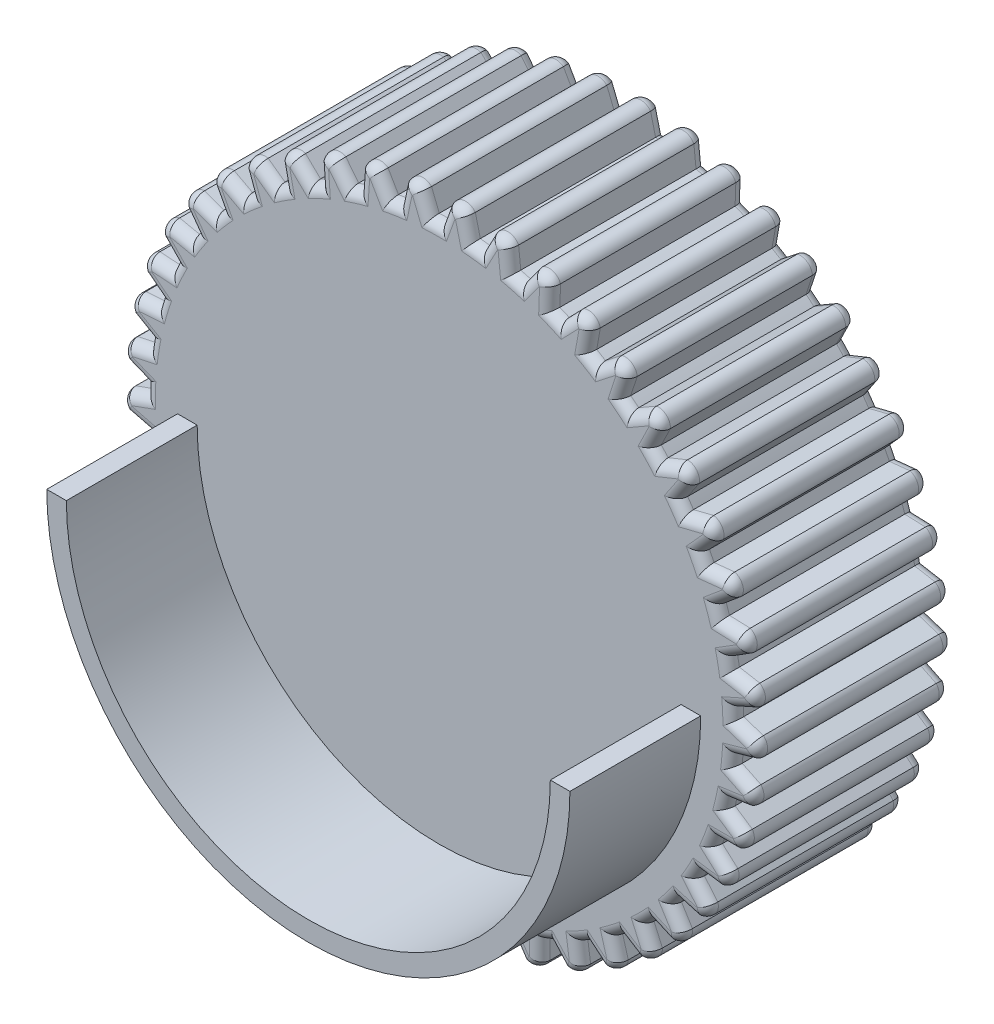
SolidWorks part; units mm, degrees
ref_plane "Front Plane" through (0, 0, 0) normal (0, 0, 1) x (1, 0, 0)
ref_plane "Top Plane" through (0, 0, 0) normal (0, 1, 0) x (1, 0, 0)
ref_plane "Right Plane" through (0, 0, 0) normal (1, 0, 0) x (0, 0, -1)
sketch "Sketch1" plane through (0, 0, 0) normal (0, 0, 1) x (1, 0, 0)
  circle A0 centre (0, 0) radius 22.5
  dimension "D1" = 45
extrude "Boss-Extrude1" add sketch "Sketch1" along normal blind 15
sketch "Sketch2" plane through (0, 0, 15) normal (0, 0, 1) x (1, 0, 0)
  circle A0 centre (0, 0) radius 20.25
  circle A1 centre (0, 0) radius 18.5
  dimension "D1" = 40.5
  dimension "D2" = 37
extrude "Boss-Extrude2" add sketch "Sketch2" along normal blind 10
sketch "Sketch3" plane through (0, 0, 15) normal (0, 0, 1) x (1, 0, 0)
  line L0 (0, 22.5) -> (0.5437, 23.9938)
  line L2 (2.3519, 22.3767) -> (1.9673, 23.9192)
  line L3 (0, 0) -> (0, 22.5)
  line L4 (2.3519, 22.3767) -> (0, 0)
  line L5 (0.5437, 23.9938) -> (1.9673, 23.9192)
  line L6 (0, 22.5) -> (0.5437, 23.9938)
  line L7 (1.9673, 23.9192) -> (2.3519, 22.3767)
  line L8 (3.1314, 22.281) -> (3.8777, 23.6847)
  line L9 (3.8777, 23.6847) -> (5.2771, 23.4127)
  line L10 (5.4432, 21.8317) -> (5.2771, 23.4127)
  line L11 (6.2018, 21.6284) -> (7.1362, 22.9145)
  line L12 (7.1362, 22.9145) -> (8.4841, 22.4504)
  line L13 (8.4286, 20.8616) -> (8.4841, 22.4504)
  line L14 (9.1516, 20.5548) -> (10.2559, 21.6983)
  line L15 (10.2559, 21.6983) -> (11.5261, 21.0511)
  line L16 (11.25, 19.4856) -> (11.5261, 21.0511)
  line L17 (11.9232, 19.0811) -> (13.1759, 20.0598)
  line L18 (13.1759, 20.0598) -> (14.3436, 19.2421)
  line L19 (13.8524, 17.7302) -> (14.3436, 19.2421)
  line L20 (14.4627, 17.236) -> (15.8395, 18.0309)
  line L21 (15.8395, 18.0309) -> (16.882, 17.0586)
  line L22 (16.1851, 15.6298) -> (16.882, 17.0586)
  line L23 (16.7208, 15.0554) -> (18.1947, 15.651)
  line L24 (18.1947, 15.651) -> (19.0918, 14.5431)
  line L25 (18.2029, 13.2252) -> (19.0918, 14.5431)
  line L26 (18.6533, 12.5818) -> (20.1958, 12.9664)
  line L27 (20.1958, 12.9664) -> (20.93, 11.7445)
  line L28 (19.8663, 10.5631) -> (20.93, 11.7445)
  line L29 (20.2229, 9.8634) -> (21.8039, 10.0295)
  line L30 (21.8039, 10.0295) -> (22.3609, 8.7173)
  line L31 (21.1431, 7.6955) -> (22.3609, 8.7173)
  line L32 (21.3988, 6.9529) -> (22.9875, 6.8974)
  line L33 (22.9875, 6.8974) -> (23.3565, 5.5204)
  line L34 (22.0083, 4.678) -> (23.3565, 5.5204)
  line L35 (22.1582, 3.9071) -> (23.7237, 3.631)
  line L36 (23.7237, 3.631) -> (23.8975, 2.2161)
  line L37 (22.4452, 1.5695) -> (23.8975, 2.2161)
  line L38 (22.4863, 0.7852) -> (23.9982, 0.294)
  line L39 (23.9982, 0.294) -> (23.9733, -1.1313)
  line L40 (22.4452, -1.5695) -> (23.9733, -1.1313)
  line L41 (22.3767, -2.3519) -> (23.8056, -3.0488)
  line L42 (23.8056, -3.0488) -> (23.5826, -4.4568)
  line L43 (22.0083, -4.678) -> (23.5826, -4.4568)
  line L44 (21.8317, -5.4432) -> (23.1496, -6.3322)
  line L45 (23.1496, -6.3322) -> (22.7328, -7.6955)
  line L46 (21.1431, -7.6955) -> (22.7328, -7.6955)
  line L47 (20.8616, -8.4286) -> (22.043, -9.4924)
  line L48 (22.043, -9.4924) -> (21.4406, -10.7844)
  line L49 (19.8663, -10.5631) -> (21.4406, -10.7844)
  line L50 (19.4856, -11.25) -> (20.5074, -12.4678)
  line L51 (20.5074, -12.4678) -> (19.731, -13.6634)
  line L52 (18.2029, -13.2252) -> (19.731, -13.6634)
  line L53 (17.7302, -13.8524) -> (18.5727, -15.2005)
  line L54 (18.5727, -15.2005) -> (17.6374, -16.2764)
  line L55 (16.1851, -15.6298) -> (17.6374, -16.2764)
  line L56 (15.6298, -16.1851) -> (16.2764, -17.6374)
  line L57 (16.2764, -17.6374) -> (15.2005, -18.5727)
  line L58 (13.8524, -17.7302) -> (15.2005, -18.5727)
  line L59 (13.2252, -18.2029) -> (13.6634, -19.731)
  line L60 (13.6634, -19.731) -> (12.4678, -20.5074)
  line L61 (11.25, -19.4856) -> (12.4678, -20.5074)
  line L62 (10.5631, -19.8663) -> (10.7844, -21.4406)
  line L63 (10.7844, -21.4406) -> (9.4924, -22.043)
  line L64 (8.4286, -20.8616) -> (9.4924, -22.043)
  line L65 (7.6955, -21.1431) -> (7.6955, -22.7328)
  line L66 (7.6955, -22.7328) -> (6.3322, -23.1496)
  line L67 (5.4432, -21.8317) -> (6.3322, -23.1496)
  line L68 (4.678, -22.0083) -> (4.4568, -23.5826)
  line L69 (4.4568, -23.5826) -> (3.0488, -23.8056)
  line L70 (2.3519, -22.3767) -> (3.0488, -23.8056)
  line L71 (1.5695, -22.4452) -> (1.1313, -23.9733)
  line L72 (1.1313, -23.9733) -> (-0.294, -23.9982)
  line L73 (-0.7852, -22.4863) -> (-0.294, -23.9982)
  line L74 (-1.5695, -22.4452) -> (-2.2161, -23.8975)
  line L75 (-2.2161, -23.8975) -> (-3.631, -23.7237)
  line L76 (-3.9071, -22.1582) -> (-3.631, -23.7237)
  line L77 (-4.678, -22.0083) -> (-5.5204, -23.3565)
  line L78 (-5.5204, -23.3565) -> (-6.8974, -22.9875)
  line L79 (-6.9529, -21.3988) -> (-6.8974, -22.9875)
  line L80 (-7.6955, -21.1431) -> (-8.7173, -22.3609)
  line L81 (-8.7173, -22.3609) -> (-10.0295, -21.8039)
  line L82 (-9.8634, -20.2229) -> (-10.0295, -21.8039)
  line L83 (-10.5631, -19.8663) -> (-11.7445, -20.93)
  line L84 (-11.7445, -20.93) -> (-12.9664, -20.1958)
  line L85 (-12.5818, -18.6533) -> (-12.9664, -20.1958)
  line L86 (-13.2252, -18.2029) -> (-14.5431, -19.0918)
  line L87 (-14.5431, -19.0918) -> (-15.651, -18.1947)
  line L88 (-15.0554, -16.7208) -> (-15.651, -18.1947)
  line L89 (-15.6298, -16.1851) -> (-17.0586, -16.882)
  line L90 (-17.0586, -16.882) -> (-18.0309, -15.8395)
  line L91 (-17.236, -14.4627) -> (-18.0309, -15.8395)
  line L92 (-17.7302, -13.8524) -> (-19.2421, -14.3436)
  line L93 (-19.2421, -14.3436) -> (-20.0598, -13.1759)
  line L94 (-19.0811, -11.9232) -> (-20.0598, -13.1759)
  line L95 (-19.4856, -11.25) -> (-21.0511, -11.5261)
  line L96 (-21.0511, -11.5261) -> (-21.6983, -10.2559)
  line L97 (-20.5548, -9.1516) -> (-21.6983, -10.2559)
  line L98 (-20.8616, -8.4286) -> (-22.4504, -8.4841)
  line L99 (-22.4504, -8.4841) -> (-22.9145, -7.1362)
  line L100 (-21.6284, -6.2018) -> (-22.9145, -7.1362)
  line L101 (-21.8317, -5.4432) -> (-23.4127, -5.2771)
  line L102 (-23.4127, -5.2771) -> (-23.6847, -3.8777)
  line L103 (-22.281, -3.1314) -> (-23.6847, -3.8777)
  line L104 (-22.3767, -2.3519) -> (-23.9192, -1.9673)
  line L105 (-23.9192, -1.9673) -> (-23.9938, -0.5437)
  line L106 (-22.5, 0) -> (-23.9938, -0.5437)
  line L107 (-22.4863, 0.7852) -> (-23.9602, 1.3808)
  line L108 (-23.9602, 1.3808) -> (-23.836, 2.8009)
  line L109 (-22.281, 3.1314) -> (-23.836, 2.8009)
  line L110 (-22.1582, 3.9071) -> (-23.5349, 4.7019)
  line L111 (-23.5349, 4.7019) -> (-23.2142, 6.0909)
  line L112 (-21.6284, 6.2018) -> (-23.2142, 6.0909)
  line L113 (-21.3988, 6.9529) -> (-22.6515, 7.9316)
  line L114 (-22.6515, 7.9316) -> (-22.1406, 9.2625)
  line L115 (-20.5548, 9.1516) -> (-22.1406, 9.2625)
  line L116 (-20.2229, 9.8634) -> (-21.3272, 11.0069)
  line L117 (-21.3272, 11.0069) -> (-20.6361, 12.2537)
  line L118 (-19.0811, 11.9232) -> (-20.6361, 12.2537)
  line L119 (-18.6533, 12.5818) -> (-19.5878, 13.8679)
  line L120 (-19.5878, 13.8679) -> (-18.7298, 15.0064)
  line L121 (-17.236, 14.4627) -> (-18.7298, 15.0064)
  line L122 (-16.7208, 15.0554) -> (-17.4671, 16.4591)
  line L123 (-17.4671, 16.4591) -> (-16.4591, 17.4671)
  line L124 (-15.0554, 16.7208) -> (-16.4591, 17.4671)
  line L125 (-14.4627, 17.236) -> (-15.0064, 18.7298)
  line L126 (-15.0064, 18.7298) -> (-13.8679, 19.5878)
  line L127 (-12.5818, 18.6533) -> (-13.8679, 19.5878)
  line L128 (-11.9232, 19.0811) -> (-12.2537, 20.6361)
  line L129 (-12.2537, 20.6361) -> (-11.0069, 21.3272)
  line L130 (-9.8634, 20.2229) -> (-11.0069, 21.3272)
  line L131 (-9.1516, 20.5548) -> (-9.2625, 22.1406)
  line L132 (-9.2625, 22.1406) -> (-7.9316, 22.6515)
  line L133 (-6.9529, 21.3988) -> (-7.9316, 22.6515)
  line L134 (-6.2018, 21.6284) -> (-6.0909, 23.2142)
  line L135 (-6.0909, 23.2142) -> (-4.7019, 23.5349)
  line L136 (-3.9071, 22.1582) -> (-4.7019, 23.5349)
  line L137 (-3.1314, 22.281) -> (-2.8009, 23.836)
  line L138 (-2.8009, 23.836) -> (-1.3808, 23.9602)
  line L139 (-0.7852, 22.4863) -> (-1.3808, 23.9602)
  arc A0 (0, 22.5) -> (2.3519, 22.3767) centre (0, 0) cw
  circle A1 centre (0, 0) radius 22.5 construction
  circle A2 centre (0, 0) radius 18.5 construction
  arc A4 (0.5437, 23.9938) -> (1.9673, 23.9192) centre (1.2243, 23.3613) cw
  arc A5 (0, 22.5) -> (2.3519, 22.3767) centre (0, 0) cw
  arc A6 (3.1314, 22.281) -> (5.4432, 21.8317) centre (0, 0) cw
  arc A7 (3.8777, 23.6847) -> (5.2771, 23.4127) centre (4.4637, 22.9636) cw
  arc A8 (6.2018, 21.6284) -> (8.4286, 20.8616) centre (0, 0) cw
  arc A9 (7.1362, 22.9145) -> (8.4841, 22.4504) centre (7.6161, 22.1189) cw
  arc A10 (9.1516, 20.5548) -> (11.25, 19.4856) centre (0, 0) cw
  arc A11 (10.2559, 21.6983) -> (11.5261, 21.0511) centre (10.6204, 20.8437) cw
  arc A12 (11.9232, 19.0811) -> (13.8524, 17.7302) centre (0, 0) cw
  arc A13 (13.1759, 20.0598) -> (14.3436, 19.2421) centre (13.4179, 19.1628) cw
  arc A14 (14.4627, 17.236) -> (16.1851, 15.6298) centre (0, 0) cw
  arc A15 (15.8395, 18.0309) -> (16.882, 17.0586) centre (15.9543, 17.1089) cw
  arc A16 (16.7208, 15.0554) -> (18.2029, 13.2252) centre (0, 0) cw
  arc A17 (18.1947, 15.651) -> (19.0918, 14.5431) centre (18.1801, 14.7219) cw
  arc A18 (18.6533, 12.5818) -> (19.8663, 10.5631) centre (0, 0) cw
  arc A19 (20.1958, 12.9664) -> (20.93, 11.7445) centre (20.0521, 12.0485) cw
  arc A20 (20.2229, 9.8634) -> (21.1431, 7.6955) centre (0, 0) cw
  arc A21 (21.8039, 10.0295) -> (22.3609, 8.7173) centre (21.5337, 9.1405) cw
  arc A22 (21.3988, 6.9529) -> (22.0083, 4.678) centre (0, 0) cw
  arc A23 (22.9875, 6.8974) -> (23.3565, 5.5204) centre (22.5963, 6.0547) cw
  arc A24 (22.1582, 3.9071) -> (22.4452, 1.5695) centre (0, 0) cw
  arc A25 (23.7237, 3.631) -> (23.8975, 2.2161) centre (23.219, 2.8509) cw
  arc A26 (22.4863, 0.7852) -> (22.4452, -1.5695) centre (0, 0) cw
  arc A27 (23.9982, 0.294) -> (23.9733, -1.1313) centre (23.3898, -0.4083) cw
  arc A28 (22.3767, -2.3519) -> (22.0083, -4.678) centre (0, 0) cw
  arc A29 (23.8056, -3.0488) -> (23.5826, -4.4568) centre (23.1054, -3.6595) cw
  arc A30 (21.8317, -5.4432) -> (21.1431, -7.6955) centre (0, 0) cw
  arc A31 (23.1496, -6.3322) -> (22.7328, -7.6955) centre (22.3712, -6.8396) cw
  arc A32 (20.8616, -8.4286) -> (19.8663, -10.5631) centre (0, 0) cw
  arc A33 (22.043, -9.4924) -> (21.4406, -10.7844) centre (21.2016, -9.8865) cw
  arc A34 (19.4856, -11.25) -> (18.2029, -13.2252) centre (0, 0) cw
  arc A35 (20.5074, -12.4678) -> (19.731, -13.6634) centre (19.6194, -12.741) cw
  arc A36 (17.7302, -13.8524) -> (16.1851, -15.6298) centre (0, 0) cw
  arc A37 (18.5727, -15.2005) -> (17.6374, -16.2764) centre (17.6552, -15.3475) cw
  arc A38 (15.6298, -16.1851) -> (13.8524, -17.7302) centre (0, 0) cw
  arc A39 (16.2764, -17.6374) -> (15.2005, -18.5727) centre (15.3475, -17.6552) cw
  arc A40 (13.2252, -18.2029) -> (11.25, -19.4856) centre (0, 0) cw
  arc A41 (13.6634, -19.731) -> (12.4678, -20.5074) centre (12.741, -19.6194) cw
  arc A42 (10.5631, -19.8663) -> (8.4286, -20.8616) centre (0, 0) cw
  arc A43 (10.7844, -21.4406) -> (9.4924, -22.043) centre (9.8865, -21.2016) cw
  arc A44 (7.6955, -21.1431) -> (5.4432, -21.8317) centre (0, 0) cw
  arc A45 (7.6955, -22.7328) -> (6.3322, -23.1496) centre (6.8396, -22.3712) cw
  arc A46 (4.678, -22.0083) -> (2.3519, -22.3767) centre (0, 0) cw
  arc A47 (4.4568, -23.5826) -> (3.0488, -23.8056) centre (3.6595, -23.1054) cw
  arc A48 (1.5695, -22.4452) -> (-0.7852, -22.4863) centre (0, 0) cw
  arc A49 (1.1313, -23.9733) -> (-0.294, -23.9982) centre (0.4083, -23.3898) cw
  arc A50 (-1.5695, -22.4452) -> (-3.9071, -22.1582) centre (0, 0) cw
  arc A51 (-2.2161, -23.8975) -> (-3.631, -23.7237) centre (-2.8509, -23.219) cw
  arc A52 (-4.678, -22.0083) -> (-6.9529, -21.3988) centre (0, 0) cw
  arc A53 (-5.5204, -23.3565) -> (-6.8974, -22.9875) centre (-6.0547, -22.5963) cw
  arc A54 (-7.6955, -21.1431) -> (-9.8634, -20.2229) centre (0, 0) cw
  arc A55 (-8.7173, -22.3609) -> (-10.0295, -21.8039) centre (-9.1405, -21.5337) cw
  arc A56 (-10.5631, -19.8663) -> (-12.5818, -18.6533) centre (0, 0) cw
  arc A57 (-11.7445, -20.93) -> (-12.9664, -20.1958) centre (-12.0485, -20.0521) cw
  arc A58 (-13.2252, -18.2029) -> (-15.0554, -16.7208) centre (0, 0) cw
  arc A59 (-14.5431, -19.0918) -> (-15.651, -18.1947) centre (-14.7219, -18.1801) cw
  arc A60 (-15.6298, -16.1851) -> (-17.236, -14.4627) centre (0, 0) cw
  arc A61 (-17.0586, -16.882) -> (-18.0309, -15.8395) centre (-17.1089, -15.9543) cw
  arc A62 (-17.7302, -13.8524) -> (-19.0811, -11.9232) centre (0, 0) cw
  arc A63 (-19.2421, -14.3436) -> (-20.0598, -13.1759) centre (-19.1628, -13.4179) cw
  arc A64 (-19.4856, -11.25) -> (-20.5548, -9.1516) centre (0, 0) cw
  arc A65 (-21.0511, -11.5261) -> (-21.6983, -10.2559) centre (-20.8437, -10.6204) cw
  arc A66 (-20.8616, -8.4286) -> (-21.6284, -6.2018) centre (0, 0) cw
  arc A67 (-22.4504, -8.4841) -> (-22.9145, -7.1362) centre (-22.1189, -7.6161) cw
  arc A68 (-21.8317, -5.4432) -> (-22.281, -3.1314) centre (0, 0) cw
  arc A69 (-23.4127, -5.2771) -> (-23.6847, -3.8777) centre (-22.9636, -4.4637) cw
  arc A70 (-22.3767, -2.3519) -> (-22.5, 0) centre (0, 0) cw
  arc A71 (-23.9192, -1.9673) -> (-23.9938, -0.5437) centre (-23.3613, -1.2243) cw
  arc A72 (-22.4863, 0.7852) -> (-22.281, 3.1314) centre (0, 0) cw
  arc A73 (-23.9602, 1.3808) -> (-23.836, 2.8009) centre (-23.3044, 2.0389) cw
  arc A74 (-22.1582, 3.9071) -> (-21.6284, 6.2018) centre (0, 0) cw
  arc A75 (-23.5349, 4.7019) -> (-23.2142, 6.0909) centre (-22.7938, 5.2624) cw
  arc A76 (-21.3988, 6.9529) -> (-20.5548, 9.1516) centre (0, 0) cw
  arc A77 (-22.6515, 7.9316) -> (-22.1406, 9.2625) centre (-21.8396, 8.3834) cw
  arc A78 (-20.2229, 9.8634) -> (-19.0811, 11.9232) centre (0, 0) cw
  arc A79 (-21.3272, 11.0069) -> (-20.6361, 12.2537) centre (-20.4603, 11.3413) cw
  arc A80 (-18.6533, 12.5818) -> (-17.236, 14.4627) centre (0, 0) cw
  arc A81 (-19.5878, 13.8679) -> (-18.7298, 15.0064) centre (-18.6828, 14.0785) cw
  arc A82 (-16.7208, 15.0554) -> (-15.0554, 16.7208) centre (0, 0) cw
  arc A83 (-17.4671, 16.4591) -> (-16.4591, 17.4671) centre (-16.5416, 16.5416) cw
  arc A84 (-14.4627, 17.236) -> (-12.5818, 18.6533) centre (0, 0) cw
  arc A85 (-15.0064, 18.7298) -> (-13.8679, 19.5878) centre (-14.0785, 18.6828) cw
  arc A86 (-11.9232, 19.0811) -> (-9.8634, 20.2229) centre (0, 0) cw
  arc A87 (-12.2537, 20.6361) -> (-11.0069, 21.3272) centre (-11.3413, 20.4603) cw
  arc A88 (-9.1516, 20.5548) -> (-6.9529, 21.3988) centre (0, 0) cw
  arc A89 (-9.2625, 22.1406) -> (-7.9316, 22.6515) centre (-8.3834, 21.8396) cw
  arc A90 (-6.2018, 21.6284) -> (-3.9071, 22.1582) centre (0, 0) cw
  arc A91 (-6.0909, 23.2142) -> (-4.7019, 23.5349) centre (-5.2624, 22.7938) cw
  arc A92 (-3.1314, 22.281) -> (-0.7852, 22.4863) centre (0, 0) cw
  arc A93 (-2.8009, 23.836) -> (-1.3808, 23.9602) centre (-2.0389, 23.3044) cw
  point P234 (0, 0)
  circle M9 centre (0, 0) radius 22.5
  dimension "D1" = 20
  dimension "D4" = 45
  dimension "D2" = 6
  dimension "D3" = 160
extrude "Boss-Extrude3" add sketch "Sketch3" against normal up to surface (15 mm away) contours L5 L0 L2 M9 | A4 L5 | L10 L9 L8 M9 | A7 L9 | L139 L138 L137 M9 | A93 L138 | L13 L12 L11 M9 | A9 L12 | L16 L15 L14 M9 | A11 L15 | L19 L18 L17 M9 | A13 L18 | L136 L135 L134 M9 | A91 L135 | L133 L132 L131 M9 | A89 L132 | L130 L129 L128 M9 | A87 L129 | L22 L21 L20 M9 | A15 L21 | L25 L24 L23 M9 | A17 L24 | L28 L27 L26 M9 | A19 L27 | L31 L30 L29 M9 | A21 L30 | L34 L33 L32 M9 | A23 L33 | L37 L36 L35 M9 | A25 L36 | L40 L39 L38 M9 | A27 L39 | L43 L42 L41 M9 | A29 L42 | L46 L45 L44 M9 | A31 L45 | L49 L48 L47 M9 | A33 L48 | L52 L51 L50 M9 | A35 L51 | L55 L54 L53 M9 | A37 L54 | L58 L57 L56 M9 | A39 L57 | L61 L60 L59 M9 | A41 L60 | L64 L63 L62 M9 | A43 L63 | L67 L66 L65 M9 | A45 L66 | L70 L69 L68 M9 | A47 L69 | L73 L72 L71 M9 | A49 L72 | L76 L75 L74 M9 | A51 L75 | L79 L78 L77 M9 | A53 L78 | L82 L81 L80 M9 | A55 L81 | L85 L84 L83 M9 | A57 L84 | L88 L87 L86 M9 | A59 L87 | L91 L90 L89 M9 | A61 L90 | L94 L93 L92 M9 | A63 L93 | L97 L96 L95 M9 | A65 L96 | L100 L99 L98 M9 | A67 L99 | L103 L102 L101 M9 | A69 L102 | L106 L105 L104 M9 | A71 L105 | L109 L108 L107 M9 | A73 L108 | L112 L111 L110 M9 | A75 L111 | L115 L114 L113 M9 | A77 L114 | L118 L117 L116 M9 | A79 L117 | L121 L120 L119 M9 | A81 L120 | L124 L123 L122 M9 | A83 L123 | L127 L126 L125 M9 | A85 L126 region at (1.2131, 23.147, 15) region at (1.2626, 24.0919, 15) region at (-2.0202, 23.0905, 15) region at (4.4227, 22.7529, 15) region at (-2.1026, 24.0331, 15) region at (4.6033, 23.6817, 15) region at (-5.2141, 22.5847, 15) region at (7.5463, 21.9159, 15) region at (-5.4269, 23.5066, 15) region at (7.8543, 22.8106, 15) region at (-8.3065, 21.6392, 15) region at (10.5229, 20.6524, 15) region at (-8.6456, 22.5226, 15) region at (10.9525, 21.4955, 15) region at (-11.2373, 20.2726, 15) region at (13.2948, 18.9869, 15) region at (-11.696, 21.1002, 15) region at (13.8375, 19.762, 15) region at (-13.9493, 18.5114, 15) region at (15.8079, 16.9519, 15) region at (-14.5188, 19.267, 15) region at (16.4532, 17.6439, 15) region at (-16.3898, 16.3898, 15) region at (18.0133, 14.5869, 15) region at (-17.0589, 17.0589, 15) region at (18.7486, 15.1823, 15) region at (-18.5114, 13.9493, 15) region at (19.8681, 11.9379, 15) region at (-19.267, 14.5188, 15) region at (20.6791, 12.4253, 15) region at (-20.2726, 11.2373, 15) region at (21.3361, 9.0567, 15) region at (-21.1002, 11.696, 15) region at (22.2071, 9.4264, 15) region at (-21.6392, 8.3065, 15) region at (22.3889, 5.9991, 15) region at (-22.5226, 8.6456, 15) region at (23.3029, 6.244, 15) region at (-22.5847, 5.2141, 15) region at (23.006, 2.8248, 15) region at (-23.5066, 5.4269, 15) region at (23.9451, 2.9401, 15) region at (-23.0905, 2.0202, 15) region at (23.1752, -0.4045, 15) region at (-24.0331, 2.1026, 15) region at (24.1213, -0.421, 15) region at (-23.147, -1.2131, 15) region at (-24.0919, -1.2626, 15) region at (22.8934, -3.626, 15) region at (-22.7529, -4.4227, 15) region at (23.8279, -3.774, 15) region at (-23.6817, -4.6033, 15) region at (22.1659, -6.7768, 15) region at (-21.9159, -7.5463, 15) region at (23.0708, -7.0535, 15) region at (-22.8106, -7.8543, 15) region at (21.0071, -9.7958, 15) region at (-20.6524, -10.5229, 15) region at (21.8646, -10.1956, 15) region at (-21.4955, -10.9525, 15)
sketch "Sketch4" plane through (0, 0, 0) normal (1, 0, 0) x (0, 0, -1)
  line L0 (-25, 20.25) -> (-25, -20.25) construction
  line L1 (-25, 0) -> (-15, 0)
  line L2 (-25, 0) -> (-25, 24.7521)
  line L3 (-25, 24.7521) -> (-15, 24.7521)
  line L4 (-15, 0) -> (-15, 24.7521)
extrude "Cut-Extrude1" cut sketch "Sketch4" against normal through all both and the other way through all
sketch "Sketch5" plane through (0, 0, 15) normal (0, 0, 1) x (1, 0, 0)
  line L1 (-33.3456, 31.4297) -> (37.9877, 31.4297)
  line L2 (-33.3456, 31.4297) -> (-33.3456, -33.693)
  line L3 (-33.3456, -33.693) -> (37.9877, -33.693)
  line L4 (37.9877, 31.4297) -> (37.9877, -33.693)
extrude "Cut-Extrude2" cut sketch "Sketch5" along normal blind 10
fillet "Fillet1" radius 0.8 360 edges at (-1.083, 23.2233, 0) (-2.1198, 24.23, 0) (-2.9661, 23.0585, 0) (-3.5198, 22.223, 0) (-4.3045, 22.8465, 0) (-5.4714, 23.6991, 0) (-6.1464, 22.4213, 0) (-6.5784, 21.5169, 0) (-7.4422, 22.0251, 0) (-8.7164, 22.707, 0) (-9.207, 21.3477, 0) (-9.5089, 20.3919, 0) (-10.4351, 20.775, 0) (-11.7918, 21.273, 0) (-12.0884, 19.8586, 0) (-12.2544, 18.8701, 0) (-13.2249, 19.1205, 0) (-14.6377, 19.4248, 0) (-14.7346, 17.9829, 0) (-14.7613, 16.981, 0) (-15.7573, 17.0939, 0) (-17.1986, 17.1986, 0) (-17.0939, 15.7573, 0) (-16.981, 14.7613, 0) (-17.9829, 14.7346, 0) (-19.4248, 14.6377, 0) (-19.1205, 13.2249, 0) (-18.8701, 12.2544, 0) (-19.8586, 12.0884, 0) (-21.273, 11.7918, 0) (-20.775, 10.4351, 0) (-20.3919, 9.5089, 0) (-21.3477, 9.207, 0) (-22.707, 8.7164, 0) (-22.0251, 7.4422, 0) (-21.5169, 6.5784, 0) (-22.4213, 6.1464, 0) (-23.6991, 5.4714, 0) (-22.8465, 4.3045, 0) (-22.223, 3.5198, 0) (-23.0585, 2.9661, 0) (-24.23, 2.1198, 0) (-23.2233, 1.083, 0) (-22.4966, 0.3927, 0) (-23.2469, -0.2719, 0) (-24.2892, -1.2729, 0) (-23.148, -2.1596, 0) (-22.3323, -2.7421, 0) (-22.9828, -3.5046, 0) (-23.8757, -4.641, 0) (-22.6222, -5.3602, 0) (-21.7333, -5.8234, 0) (-22.2714, -6.669, 0) (-22.9974, -7.9186, 0) (-21.656, -8.4564, 0) (-20.7114, -8.7915, 0) (-21.1265, -9.7037, 0) (-21.6715, -11.0422, 0) (-20.2684, -11.388, 0) (-19.2863, -11.5884, 0) (-19.5704, -12.5495, 0) (-19.9238, -13.9508, 0) (-18.4862, -14.098, 0) (-17.4858, -14.1597, 0) (-17.6334, -15.1511, 0) (-17.7884, -16.5879, 0) (-16.3442, -16.5336, 0) (-15.345, -16.4555, 0) (-15.3532, -17.4577, 0) (-15.3067, -18.9022, 0) (-13.8841, -18.6474, 0) (-12.9055, -18.4309, 0) (-12.7741, -19.4246, 0) (-12.527, -20.8485, 0) (-11.1538, -20.3982, 0) (-10.2148, -20.0476, 0) (-9.9464, -21.0134, 0) (-9.5036, -22.389, 0) (-8.2064, -21.752, 0) (-7.3253, -21.2742, 0) (-6.9251, -22.1931, 0) (-6.2951, -23.4938, 0) (-5.0992, -22.6824, 0) (-4.2932, -22.0866, 0) (-3.7691, -22.941, 0) (-2.9642, -24.1412, 0) (-1.8928, -23.1713, 0) (-1.1776, -22.4692, 0) (-0.5396, -23.2422, 0) (0.4245, -24.3188, 0) (1.3504, -23.2093, 0) (1.961, -22.4144, 0) (2.7003, -23.0912, 0) (3.8049, -24.0231, 0) (4.5674, -22.7954, 0) (5.0614, -21.9233, 0) (5.8877, -22.4906, 0) (7.1112, -23.2597, 0) (7.6955, -21.9379, 0) (8.0633, -21.0056, 0) (8.9605, -21.4523, 0) (10.2791, -22.0437, 0) (10.6737, -20.6534, 0) (10.9082, -19.6789, 0) (11.8589, -19.9965, 0) (13.247, -20.3986, 0) (13.4443, -18.9669, 0) (13.5408, -17.9693, 0) (14.5265, -18.1515, 0) (15.957, -18.3564, 0) (15.9531, -16.9113, 0) (15.9099, -15.9099, 0) (16.9113, -15.9531, 0) (18.3564, -15.957, 0) (18.1515, -14.5265, 0) (17.9693, -13.5408, 0) (18.9669, -13.4443, 0) (20.3986, -13.247, 0) (19.9965, -11.8589, 0) (19.6789, -10.9082, 0) (20.6534, -10.6737, 0) (22.0437, -10.2791, 0) (21.4523, -8.9605, 0) (21.0056, -8.0633, 0) (21.9379, -7.6955, 0) (23.2597, -7.1112, 0) (22.4906, -5.8877, 0) (21.9233, -5.0614, 0) (22.7954, -4.5674, 0) (24.0231, -3.8049, 0) (23.0912, -2.7003, 0) (22.4144, -1.961, 0) (23.2093, -1.3504, 0) (24.3188, -0.4245, 0) (23.2422, 0.5396, 0) (22.4692, 1.1776, 0) (23.1713, 1.8928, 0) (24.1412, 2.9642, 0) (22.941, 3.7691, 0) (22.0866, 4.2932, 0) (22.6824, 5.0992, 0) (23.4938, 6.2951, 0) (22.1931, 6.9251, 0) (21.2742, 7.3253, 0) (21.752, 8.2064, 0) (22.389, 9.5036, 0) (21.0134, 9.9464, 0) (20.0476, 10.2148, 0) (20.3982, 11.1538, 0) (20.8485, 12.527, 0) (19.4246, 12.7741, 0) (18.4309, 12.9055, 0) (18.6474, 13.8841, 0) (18.9022, 15.3067, 0) (17.4577, 15.3532, 0) (16.4555, 15.345, 0) (16.5336, 16.3442, 0) (16.5879, 17.7884, 0) (15.1511, 17.6334, 0) (14.1597, 17.4858, 0) (14.098, 18.4862, 0) (13.9508, 19.9238, 0) (12.5495, 19.5704, 0) (11.5884, 19.2863, 0) (11.388, 20.2684, 0) (11.0422, 21.6715, 0) (9.7037, 21.1265, 0) (8.7915, 20.7114, 0) (8.4564, 21.656, 0) (7.9186, 22.9974, 0) (6.669, 22.2714, 0) (5.8234, 21.7333, 0) (5.3602, 22.6222, 0) (4.641, 23.8757, 0) (3.5046, 22.9828, 0) (2.7421, 22.3323, 0) (2.1596, 23.148, 0) (1.2729, 24.2892, 0) (0.2719, 23.2469, 0) (-0.3927, 22.4966, 0) (-23.2233, 1.083, 15) (-24.23, 2.1198, 15) (-23.0585, 2.9661, 15) (-22.223, 3.5198, 15) (-22.8465, 4.3045, 15) (-23.6991, 5.4714, 15) (-22.4213, 6.1464, 15) (-21.5169, 6.5784, 15) (-22.0251, 7.4422, 15) (-22.707, 8.7164, 15) (-21.3477, 9.207, 15) (-20.3919, 9.5089, 15) (-20.775, 10.4351, 15) (-21.273, 11.7918, 15) (-19.8586, 12.0884, 15) (-18.8701, 12.2544, 15) (-19.1205, 13.2249, 15) (-19.4248, 14.6377, 15) (-17.9829, 14.7346, 15) (-16.981, 14.7613, 15) (-17.0939, 15.7573, 15) (-17.1986, 17.1986, 15) (-15.7573, 17.0939, 15) (-14.7613, 16.981, 15) (-14.7346, 17.9829, 15) (-14.6377, 19.4248, 15) (-13.2249, 19.1205, 15) (-12.2544, 18.8701, 15) (-12.0884, 19.8586, 15) (-11.7918, 21.273, 15) (-10.4351, 20.775, 15) (-9.5089, 20.3919, 15) (-9.207, 21.3477, 15) (-8.7164, 22.707, 15) (-7.4422, 22.0251, 15) (-6.5784, 21.5169, 15) (-6.1464, 22.4213, 15) (-5.4714, 23.6991, 15) (-4.3045, 22.8465, 15) (-3.5198, 22.223, 15) (-2.9661, 23.0585, 15) (-2.1198, 24.23, 15) (-1.083, 23.2233, 15) (-0.3927, 22.4966, 15) (0.2719, 23.2469, 15) (1.2729, 24.2892, 15) (2.1596, 23.148, 15) (2.7421, 22.3323, 15) (3.5046, 22.9828, 15) (4.641, 23.8757, 15) (5.3602, 22.6222, 15) (5.8234, 21.7333, 15) (6.669, 22.2714, 15) (7.9186, 22.9974, 15) (8.4564, 21.656, 15) (8.7915, 20.7114, 15) (9.7037, 21.1265, 15) (11.0422, 21.6715, 15) (11.388, 20.2684, 15) (11.5884, 19.2863, 15) (12.5495, 19.5704, 15) (13.9508, 19.9238, 15) (14.098, 18.4862, 15) (14.1597, 17.4858, 15) (15.1511, 17.6334, 15) (16.5879, 17.7884, 15) (16.5336, 16.3442, 15) (16.4555, 15.345, 15) (17.4577, 15.3532, 15) (18.9022, 15.3067, 15) (18.6474, 13.8841, 15) (18.4309, 12.9055, 15) (19.4246, 12.7741, 15) (20.8485, 12.527, 15) (20.3982, 11.1538, 15) (20.0476, 10.2148, 15) (21.0134, 9.9464, 15) (22.389, 9.5036, 15) (21.752, 8.2064, 15) (21.2742, 7.3253, 15) (22.1931, 6.9251, 15) (23.4938, 6.2951, 15) (22.6824, 5.0992, 15) (22.0866, 4.2932, 15) (22.941, 3.7691, 15) (24.1412, 2.9642, 15) (23.1713, 1.8928, 15) (22.4692, 1.1776, 15) (23.2422, 0.5396, 15) (24.3188, -0.4245, 15) (23.2093, -1.3504, 15) (22.4144, -1.961, 15) (23.0912, -2.7003, 15) (24.0231, -3.8049, 15) (22.7954, -4.5674, 15) (21.9233, -5.0614, 15) (22.4906, -5.8877, 15) (23.2597, -7.1112, 15) (21.9379, -7.6955, 15) (21.0056, -8.0633, 15) (21.4523, -8.9605, 15) (22.0437, -10.2791, 15) (20.6534, -10.6737, 15) (19.6789, -10.9082, 15) (19.9965, -11.8589, 15) (20.3986, -13.247, 15) (18.9669, -13.4443, 15) (17.9693, -13.5408, 15) (18.1515, -14.5265, 15) (18.3564, -15.957, 15) (16.9113, -15.9531, 15) (15.9099, -15.9099, 15) (15.9531, -16.9113, 15) (15.957, -18.3564, 15) (14.5265, -18.1515, 15) (13.5408, -17.9693, 15) (13.4443, -18.9669, 15) (13.247, -20.3986, 15) (11.8589, -19.9965, 15) (10.9082, -19.6789, 15) (10.6737, -20.6534, 15) (10.2791, -22.0437, 15) (8.9605, -21.4523, 15) (8.0633, -21.0056, 15) (7.6955, -21.9379, 15) (7.1112, -23.2597, 15) (5.8877, -22.4906, 15) (5.0614, -21.9233, 15) (4.5674, -22.7954, 15) (3.8049, -24.0231, 15) (2.7003, -23.0912, 15) (1.961, -22.4144, 15) (1.3504, -23.2093, 15) (0.4245, -24.3188, 15) (-0.5396, -23.2422, 15) (-1.1776, -22.4692, 15) (-1.8928, -23.1713, 15) (-2.9642, -24.1412, 15) (-3.7691, -22.941, 15) (-4.2932, -22.0866, 15) (-5.0992, -22.6824, 15) (-6.2951, -23.4938, 15) (-6.9251, -22.1931, 15) (-7.3253, -21.2742, 15) (-8.2064, -21.752, 15) (-9.5036, -22.389, 15) (-9.9464, -21.0134, 15) (-10.2148, -20.0476, 15) (-11.1538, -20.3982, 15) (-12.527, -20.8485, 15) (-12.7741, -19.4246, 15) (-12.9055, -18.4309, 15) (-13.8841, -18.6474, 15) (-15.3067, -18.9022, 15) (-15.3532, -17.4577, 15) (-15.345, -16.4555, 15) (-16.3442, -16.5336, 15) (-17.7884, -16.5879, 15) (-17.6334, -15.1511, 15) (-17.4858, -14.1597, 15) (-18.4862, -14.098, 15) (-19.9238, -13.9508, 15) (-19.5704, -12.5495, 15) (-19.2863, -11.5884, 15) (-20.2684, -11.388, 15) (-21.6715, -11.0422, 15) (-21.1265, -9.7037, 15) (-20.7114, -8.7915, 15) (-21.656, -8.4564, 15) (-22.9974, -7.9186, 15) (-22.2714, -6.669, 15) (-21.7333, -5.8234, 15) (-22.6222, -5.3602, 15) (-23.8757, -4.641, 15) (-22.9828, -3.5046, 15) (-22.3323, -2.7421, 15) (-23.148, -2.1596, 15) (-24.2892, -1.2729, 15) (-23.2469, -0.2719, 15) (-22.4966, 0.3927, 15)
sketch "Sketch6" plane through (0, 0, 15) normal (0, 0, 1) x (1, 0, 0)
  circle A0 centre (0, 0) radius 20
  circle A1 centre (0, 0) radius 18.5
  dimension "D1" = 40
  dimension "D2" = 37
extrude "Boss-Extrude4" add sketch "Sketch6" along normal blind 10
sketch "Sketch7" plane through (0, 0, 15) normal (0, 0, 1) x (1, 0, 0)
  line L1 (-20, 0) -> (20, 0)
  line L2 (-20, 0) -> (-20, 24.8115)
  line L3 (-20, 24.8115) -> (20, 24.8115)
  line L4 (20, 0) -> (20, 24.8115)
  circle A0 centre (0, 0) radius 20 construction
  circle A1 centre (0, 0) radius 20 construction
extrude "Cut-Extrude3" cut sketch "Sketch7" along normal blind 10
sketch "Sketch8" plane through (0, 0, 0) normal (0, 0, -1) x (-1, 0, 0)
  circle A0 centre (0, 0) radius 20.25
  circle A1 centre (0, 0) radius 12.5
  dimension "D1" = 25
  dimension "D2" = 40.5
extrude "Cut-Extrude4" cut sketch "Sketch8" against normal blind 10.5
